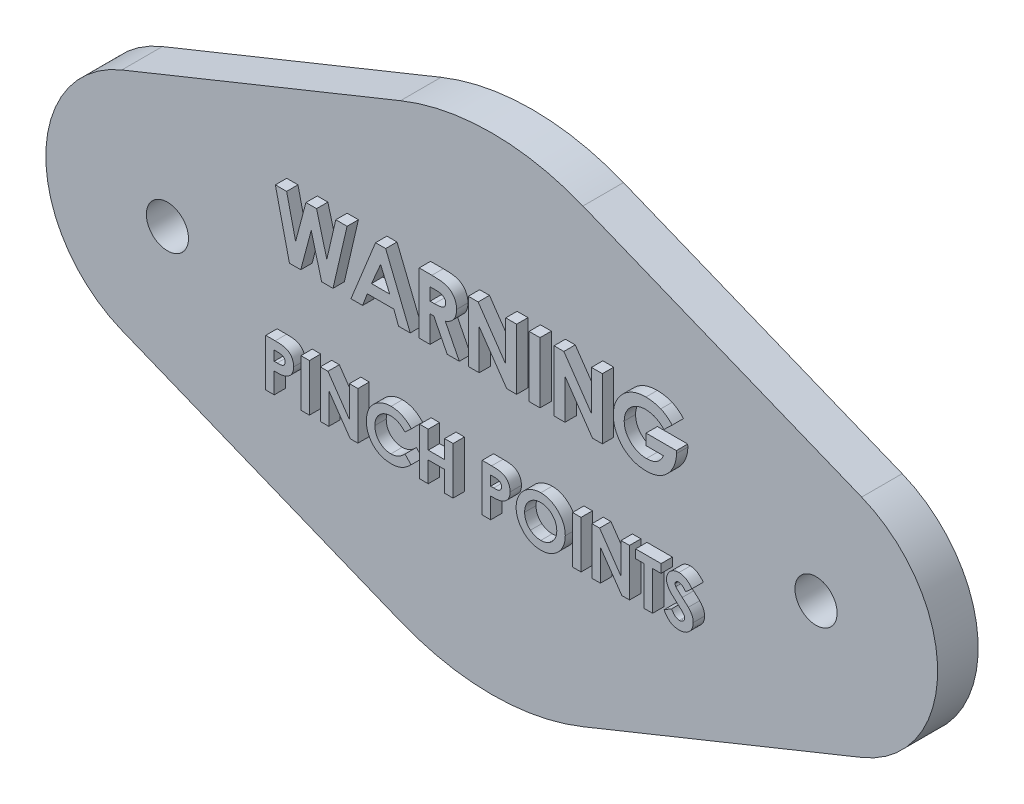
SolidWorks part; units mm, degrees
ref_plane "Front Plane" through (0, 0, 0) normal (0, 0, 1) x (1, 0, 0)
ref_plane "Top Plane" through (0, 0, 0) normal (0, 1, 0) x (1, 0, 0)
ref_plane "Right Plane" through (0, 0, 0) normal (1, 0, 0) x (0, 0, -1)
sketch "Sketch1" plane through (0, 0, 0) normal (0, 0, 1) x (1, 0, 0)
  line L0 (-69.85, 0) -> (69.85, 0) construction
  line L1 (0, -38.1) -> (0, 38.1) construction
  line L2 (-57.9437, 17.6598) -> (-14.2875, 35.3196)
  line L3 (14.2875, 35.3196) -> (57.9437, 17.6598)
  line L4 (14.2875, -35.3196) -> (57.9437, -17.6598)
  line L5 (-57.9437, -17.6598) -> (-14.2875, -35.3196)
  circle A0 centre (-50.8, 0) radius 19.05
  circle A1 centre (50.8, 0) radius 19.05
  circle A2 centre (0, 0) radius 38.1
  point P4 (0, 0)
  point P8 (0, 0)
  dimension "D3" = 38.1
  dimension "D4" = 76.2
  dimension "D1" = 139.7
  dimension "D2" = 76.2
extrude "Boss-Extrude1" add sketch "Sketch1" along normal blind 6.35 contours A2 A0 | A0 A2 | A2 L2 A0 | A1 A2 A0 | A2 A0 L5 | A2 L4 A1 | A1 A2 | A2 A1 | A2 A1 L3 region at (-52.3838, 0, 0) region at (-36.9049, 22.1448, 0) region at (0, 0, 0) region at (-36.9049, -22.1448, 0) region at (-35.1402, 0, 0) region at (36.9049, 22.1448, 0) region at (52.3838, 0, 0) region at (35.1402, 0, 0) region at (36.9049, -22.1448, 0)
sketch "Sketch2" plane through (0, 0, 6.35) normal (0, 0, 1) x (1, 0, 0)
  circle A0 centre (-50.8, 0) radius 3.302
  circle A1 centre (50.8, 0) radius 3.302
  dimension "D1" = 6.604
  dimension "D2" = 6.604
extrude "Cut-Extrude1" cut sketch "Sketch2" against normal through all
sketch "Sketch3" plane through (0, 0, 6.35) normal (0, 0, 1) x (1, 0, 0)
  line L0 (-35.6938, 6.35) -> (35.6938, 6.35) construction
  line L1 (0, 0) -> (27.0929, 0) construction
  line L2 (-35.6938, -12.7) -> (35.6938, -12.7) construction
  text T0 "<b>WARNING</b>" font "Century Gothic" height in points 36
  text T1 "<b>PINCH POINTS</b>" font "Century Gothic" height in points 28
  point P2 (0, 6.35)
  dimension "D1" = 6.35
  dimension "D2" = 12.7
extrude "Cut-Extrude2" cut sketch "Sketch3" against normal blind 0.254
extrude "Boss-Extrude2" add sketch "Sketch3<2>" against normal blind 0.254 and the other way blind 1.778 separate body
sketch "Sketch3<2>" plane through (0, 0, 6.35) normal (0, 0, 1) x (1, 0, 0) same geometry as "Sketch3"
